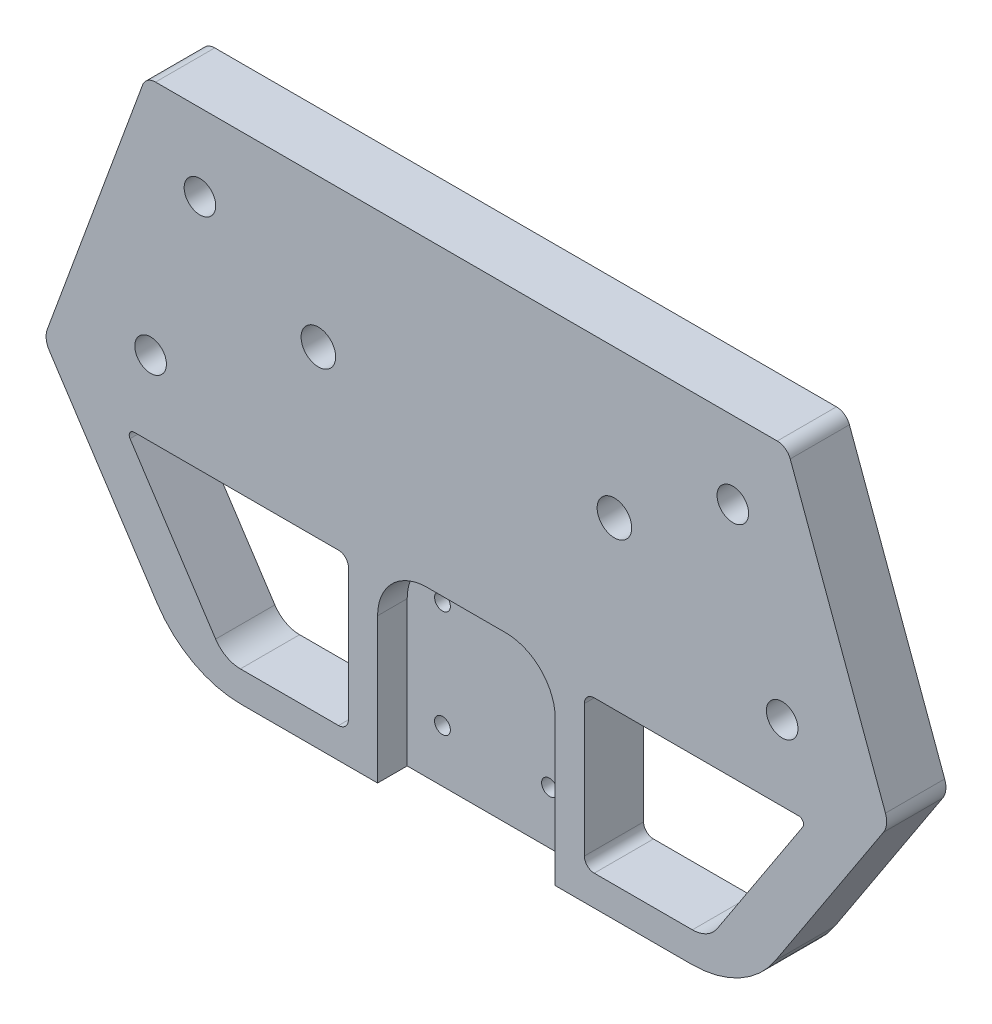
SolidWorks part; units mm, degrees
ref_plane "Front Plane" through (0, 0, 0) normal (0, 0, 1) x (1, 0, 0)
ref_plane "Top Plane" through (0, 0, 0) normal (0, 1, 0) x (1, 0, 0)
ref_plane "Right Plane" through (0, 0, 0) normal (1, 0, 0) x (0, 0, -1)
sketch "Sketch2" plane through (0, 0, 0) normal (0, 0, 1) x (1, 0, 0)
  line L0 (0, -44.7145) -> (0, 43.9236) construction
  line L3 (-53.9331, -0.3154) -> (-41.6738, 33.03)
  line L5 (-53.6746, -2.5826) -> (-39.7807, -23.8164)
  line L8 (-28.9986, -29.6465) -> (28.9986, -29.6465)
  line L9 (-40.005, 34.1945) -> (40.005, 34.1945)
  line L10 (53.6746, -2.5826) -> (39.7807, -23.8164)
  line L11 (53.9331, -0.3154) -> (41.6738, 33.03)
  arc A1 (-40.005, 34.1945) -> (-41.6738, 33.03) centre (-40.005, 32.4165) ccw
  circle A4 centre (-19.05, 15.1445) radius 2.2225
  arc A6 (-28.9986, -29.6465) -> (-39.7807, -23.8164) centre (-28.9986, -16.7614) cw
  arc A8 (-53.6746, -2.5826) -> (-53.9331, -0.3154) centre (-51.5491, -1.1919) cw
  arc A10 (53.6746, -2.5826) -> (53.9331, -0.3154) centre (51.5491, -1.1919) ccw
  arc A11 (28.9986, -29.6465) -> (39.7807, -23.8164) centre (28.9986, -16.7614) ccw
  circle A12 centre (19.05, 15.1445) radius 2.2225
  arc A13 (40.005, 34.1945) -> (41.6738, 33.03) centre (40.005, 32.4165) cw
  point P4 (0, 57.6776)
  point P9 (0, 19.5776)
  point P12 (54.3738, -1.514)
  point P13 (0, -29.6465)
  point P19 (-35.9659, -29.6465)
  point P20 (0, -3.9055)
  point P28 (-54.3738, -1.514)
  point P33 (0, 34.1945)
  point P34 (35.9659, -29.6465)
  dimension "D2" = 1.778
  dimension "D3" = 12.8851
  dimension "D6" = 28.9986
  dimension "D4" = 2.54
  dimension "D5" = 19.05
  dimension "D7" = 35.9659
  dimension "D8" = 40.005
  dimension "D9" = 41.6738
  dimension "D10" = 51.5491
  dimension "D11" = 15.1445
  dimension "D12" = 19.5776
  dimension "D1" = 4.445
  dimension "D13" = 32.4165
  dimension "D14" = 57.6776
extrude "Boss-Extrude1" add sketch "Sketch2" along normal blind 7.62
sketch "Sketch3" plane through (0, 0, 7.62) normal (0, 0, 1) x (1, 0, 0)
  line L0 (0, 22.8554) -> (0, -43.592) construction
  line L7 (-24.13, -37.0871) -> (24.13, -37.0871) construction
  circle A0 centre (-6.887, -22.8631) radius 1.016
  circle A1 centre (-6.887, -9.0892) radius 1.016
  circle A6 centre (6.887, -9.0892) radius 1.016
  circle A7 centre (6.887, -22.8631) radius 1.016
  dimension "D4" = 14.224
  dimension "D1" = 6.887
  dimension "D2" = 13.7739
  dimension "D3" = 2.032
extrude "Cut-Extrude1" cut sketch "Sketch3" against normal through all both and the other way through all
sketch "Sketch4" plane through (0, 0, 7.62) normal (0, 0, 1) x (1, 0, 0)
  line L0 (0, 3.0374) -> (0, -49.2989) construction
  line L3 (-11.43, -37.7213) -> (11.43, -37.7213)
  line L4 (-5.08, -4.6492) -> (5.08, -4.6492)
  line L6 (-11.43, -10.9992) -> (-11.43, -37.7213)
  line L7 (11.43, -10.9992) -> (11.43, -37.7213)
  line L9 (40.005, 34.1945) -> (-40.005, 34.1945) construction
  arc A2 (-5.08, -4.6492) -> (-11.43, -10.9992) centre (-5.08, -10.9992) ccw
  arc A3 (11.43, -10.9992) -> (5.08, -4.6492) centre (5.08, -10.9992) ccw
  point P14 (0, -5.5711)
  point P17 (0, -37.7213)
  dimension "D2" = 6.35
  dimension "D1" = 13.9281
  dimension "D6" = 6.35
  dimension "D3" = 42.5031
  dimension "D4" = 38.8436
  dimension "D5" = 71.9158
extrude "Cut-Extrude2" cut sketch "Sketch4" against normal blind 3.81 and the other way through all
sketch "Sketch5" plane through (0, 0, 0) normal (0, 0, -1) x (-1, 0, 0)
  line L0 (0, -24.2327) -> (0, 20.0285) construction
  circle A0 centre (-6.887, -9.0892) radius 1.905
  circle A1 centre (-6.887, -22.8631) radius 1.905
  circle A2 centre (6.887, -22.8631) radius 1.905
  circle A3 centre (6.887, -9.0892) radius 1.905
  dimension "D1" = 3.81
  dimension "D2" = 3.81
extrude "Cut-Extrude3" cut sketch "Sketch5" against normal blind 1.3335
sketch "Sketch6" plane through (0, 0, 7.62) normal (0, 0, 1) x (1, 0, 0)
  line L0 (0, -25.1696) -> (0, 28.2164) construction
  line L3 (-43.2885, -7.1893) -> (-32.2734, -24.0235)
  line L4 (-53.6746, -2.5826) -> (-39.7807, -23.8164) construction
  line L5 (-54.0728, -1.4797) -> (0, -1.4797) construction
  line L6 (-42.7572, -6.2066) -> (-16.453, -6.2066)
  line L7 (-15.183, -7.4766) -> (-15.183, -24.4774)
  line L13 (-29.0853, -25.7474) -> (-16.453, -25.7474)
  line L14 (43.2885, -7.1893) -> (32.2734, -24.0235)
  line L17 (29.0853, -25.7474) -> (16.453, -25.7474)
  line L18 (15.183, -7.4766) -> (15.183, -24.4774)
  line L19 (42.7572, -6.2066) -> (16.453, -6.2066)
  line L20 (-11.43, -10.9992) -> (-11.43, -29.6465) construction
  line L21 (11.43, -29.6465) -> (28.9986, -29.6465) construction
  arc A3 (-53.9331, -0.3154) -> (-53.6746, -2.5826) centre (-51.5491, -1.1919) ccw construction
  arc A6 (-15.183, -7.4766) -> (-16.453, -6.2066) centre (-16.453, -7.4766) ccw
  arc A7 (-42.7572, -6.2066) -> (-43.2885, -7.1893) centre (-42.7572, -6.8416) ccw
  arc A12 (-29.0853, -25.7474) -> (-32.2734, -24.0235) centre (-29.0853, -21.9374) cw
  arc A13 (-15.183, -24.4774) -> (-16.453, -25.7474) centre (-16.453, -24.4774) cw
  arc A14 (42.7572, -6.2066) -> (43.2885, -7.1893) centre (42.7572, -6.8416) cw
  arc A15 (29.0853, -25.7474) -> (32.2734, -24.0235) centre (29.0853, -21.9374) ccw
  arc A16 (15.183, -24.4774) -> (16.453, -25.7474) centre (16.453, -24.4774) ccw
  arc A17 (15.183, -7.4766) -> (16.453, -6.2066) centre (16.453, -7.4766) cw
  point P3 (-15.183, -28.4125)
  dimension "D1" = 3.81
  dimension "D2" = 1.27
  dimension "D3" = 26.613
  dimension "D4" = 0.635
  dimension "D5" = 40.5153
  dimension "D6" = 54.1872
  dimension "D7" = 3.8991
extrude "Cut-Extrude4" cut sketch "Sketch6" against normal through all
sketch "Sketch8" plane through (0, 0, 7.62) normal (0, 0, 1) x (1, 0, 0)
  line L0 (0, 24.5882) -> (0, -31.804) construction
  line L1 (-16.453, -6.2066) -> (-42.7572, -6.2066) construction
  circle A0 centre (-40.64, 3.4454) radius 2.032
  circle A1 centre (-34.29, 24.2734) radius 2.032
  circle A2 centre (40.64, 3.4454) radius 2.032
  circle A3 centre (34.29, 24.2734) radius 2.032
  dimension "D1" = 4.064
  dimension "D2" = 4.064
  dimension "D3" = 40.64
  dimension "D4" = 34.29
  dimension "D5" = 9.652
  dimension "D6" = 30.48
extrude "Cut-Extrude6" cut sketch "Sketch8" against normal through all
sketch "Sketch9" plane through (0, 0, 0) normal (0, 0, -1) x (-1, 0, 0)
  line L0 (0, -8.3025) -> (0, 31.5976) construction
  circle A0 centre (-19.05, 15.1445) radius 3.937
  circle A1 centre (19.05, 15.1445) radius 3.937
  dimension "D1" = 7.874
extrude "Cut-Extrude7" cut sketch "Sketch9" against normal blind 2.286
